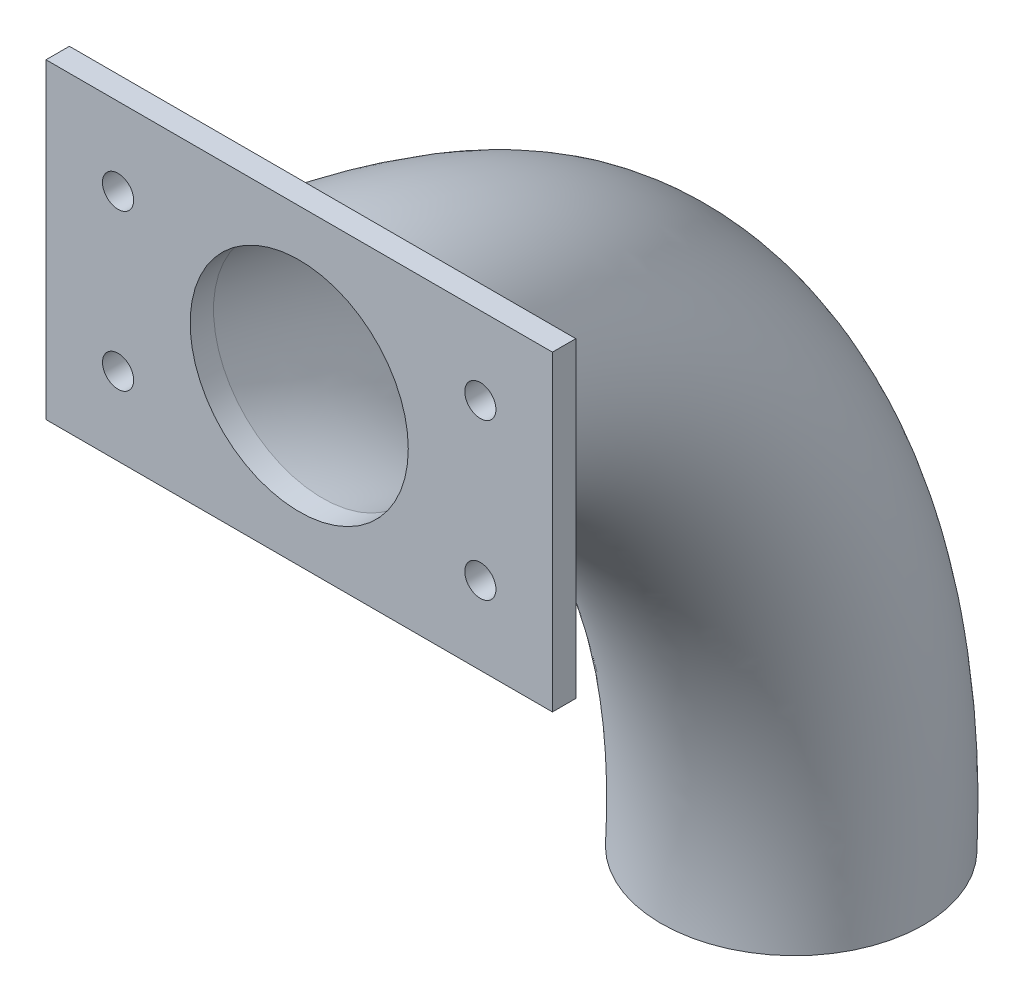
SolidWorks part; units mm, degrees
ref_plane "Plan de face" through (0, 0, 0) normal (0, 0, 1) x (1, 0, 0)
ref_plane "Plan de dessus" through (0, 0, 0) normal (0, 1, 0) x (1, 0, 0)
ref_plane "Plan de droite" through (0, 0, 0) normal (1, 0, 0) x (0, 0, -1)
sketch "Esquisse1" plane through (0, 0, 0) normal (0, 0, 1) x (1, 0, 0)
  circle A0 centre (0, 0) radius 14
  circle A1 centre (0, 0) radius 17
  dimension "D1" = 28
  dimension "D2" = 3
sketch "Esquisse2" plane through (0, 0, 0) normal (1, 0, 0) x (0, 0, -1)
  line L0 (0, 0) -> (0, -85) construction
  line L1 (0, -85) -> (60, -85) construction
  spline S0 degree 3 poles (0, 0) (10.1594, -1.9182) (29.4928, -7.7952) (55.4073, -37.6524) (61.4111, -66.1664) (60, -85) knots 0 0 0 0 0.272464 0.506576 1 1 1 1
  dimension "D1" = 85
  dimension "D2" = 60
sweep "Balayage1" add profiles "Esquisse1" path "Esquisse2"
ref_plane "Plan1" through (0, -83, 0) normal (0, 1, 0) x (1, 0, 0)
sketch "Esquisse3" plane through (0, -83, 0) normal (0, 1, 0) x (1, 0, 0)
  line L1 (35.0227, 91.4102) -> (-35.0227, 91.4102)
  line L2 (35.0227, 91.4102) -> (35.0227, 31.3519)
  line L3 (35.0227, 31.3519) -> (-35.0227, 31.3519)
  line L4 (-35.0227, 91.4102) -> (-35.0227, 31.3519)
  line L5 (35.0227, 91.4102) -> (-35.0227, 31.3519) construction
  line L6 (35.0227, 31.3519) -> (-35.0227, 91.4102) construction
  point P0 (0, 61.381)
extrude "Enlèv. mat.-Extru.1" cut sketch "Esquisse3" against normal blind 10
sketch "Esquisse4" plane through (0, 0, 0) normal (0, 0, 1) x (1, 0, 0)
  line L0 (-14, 0) -> (-32.5, 0) construction
  line L1 (-32.5, -20) -> (32.5, -20)
  line L2 (-32.5, -20) -> (-32.5, 20)
  line L3 (-32.5, 20) -> (32.5, 20)
  line L4 (32.5, -20) -> (32.5, 20)
  line L5 (-32.5, -20) -> (32.5, 20) construction
  line L6 (-32.5, 20) -> (32.5, -20) construction
  line L7 (-23.25, 0) -> (-23.25, 20) construction
  line L8 (0, 20) -> (0, -20) construction
  circle A0 centre (0, 0) radius 14
  circle A1 centre (-23.25, 10) radius 2
  circle A2 centre (-23.25, -10) radius 2
  circle A3 centre (23.25, -10) radius 2
  circle A4 centre (23.25, 10) radius 2
  point P0 (0, 0)
  dimension "D3" = 4
  dimension "D4" = 9.25
  dimension "D1" = 65
  dimension "D2" = 40
extrude "Boss.-Extru.1" add sketch "Esquisse4" along normal blind 3
